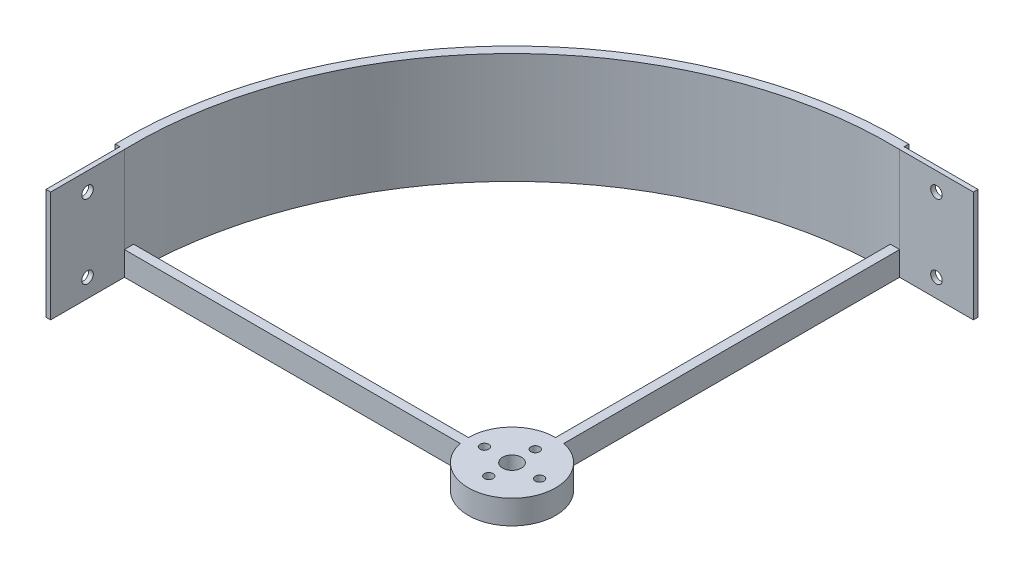
SolidWorks part; units mm, degrees
material "ABS"
ref_plane "Front Plane" through (0, 0, 0) normal (0, 0, 1) x (1, 0, 0)
ref_plane "Top Plane" through (0, 0, 0) normal (0, 1, 0) x (1, 0, 0)
ref_plane "Right Plane" through (0, 0, 0) normal (1, 0, 0) x (0, 0, -1)
sketch "Sketch1" plane through (0, 0, 0) normal (0, 1, 0) x (1, 0, 0)
  line L0 (0, 130.175) -> (0, 9.3426)
  line L1 (3.175, 9.3426) -> (3.175, 130.1363)
  line L2 (0, 0) -> (-22.0351, 22.0351) construction
  line L3 (-22.0351, 22.0351) -> (23.6345, -23.6345) construction
  line L4 (-9.3426, -3.175) -> (-130.1363, -3.175)
  line L5 (-130.175, 0) -> (-9.3426, 0)
  line L6 (3.175, 9.3426) -> (3.175, 130.1363)
  line L7 (3.175, 130.1363) -> (3.175, 133.3122)
  line L8 (-130.1363, -3.175) -> (-133.3122, -3.175)
  circle A0 centre (0, 0) radius 15
  arc A1 (3.175, 130.1363) -> (-130.1363, -3.175) centre (0, 0) ccw
  arc A2 (3.175, 133.3122) -> (-133.3122, -3.175) centre (0, 0) ccw
  dimension "D1" = 30
  dimension "D2" = 133.35
  dimension "D4" = 3.175
  dimension "D3" = 3.175
extrude "Boss-Extrude2" add sketch "Sketch1" along normal blind 8.255 contours A0
extrude "Boss-Extrude3" add sketch "Sketch1<6>" along normal blind 8.255 contours L5 A1 L4 A0 | L6 A1 L0 A0 region at (1.5882, 0, -72.5246) region at (-72.5246, 0, 1.5882)
sketch "Sketch1<6>" plane through (0, 0, 0) normal (0, 1, 0) x (1, 0, 0) same geometry as "Sketch1"
extrude "Boss-Extrude4" add sketch "Sketch1<7>" along normal blind 38.1 contours L7 A2 L8 A1 region at (-93.4129, 0, -93.4129)
sketch "Sketch1<7>" plane through (0, 0, 0) normal (0, 1, 0) x (1, 0, 0) same geometry as "Sketch1"
ref_plane "Plane1" through (-63.4806, 0, -63.4806) normal (0.7071, 0, 0.7071) x (0.7071, 0, -0.7071)
sketch "Sketch5" plane through (0, 8.255, 0) normal (0, 1, 0) x (1, 0, 0)
  line L0 (0, 0) -> (29.635, 0) construction
  line L1 (0, 0) -> (0, 21.5427) construction
  line L2 (0, 130.175) -> (0, 15) construction
  line L3 (0, 0) -> (29.22, 0) construction
  line L4 (21.3608, 0) -> (-27.7675, 0) construction
  line L5 (0, 0) -> (0, 21.6948) construction
  line L6 (0, 8) -> (0, 0) construction
  line L7 (0, 0) -> (37.8993, -60.1598) construction
  line L8 (0, 0) -> (-19.6346, 0) construction
  line L9 (-130.175, 0) -> (-15, 0) construction
  circle A0 centre (-9.5, 0) radius 1.5
  circle A1 centre (0, 8) radius 1.5
  circle A2 centre (0, -8) radius 1.5
  circle A3 centre (9.5, 0) radius 1.5
  circle A6 centre (0, 0) radius 3.25
  point P18 (0, 0)
  dimension "D3" = 3
  dimension "D7" = 3
  dimension "D8" = 6.5
  dimension "D2" = 8
  dimension "D5" = 90
  dimension "D6" = 8
  dimension "D9" = 90
  dimension "D10" = 9.5
  dimension "D4" = 57.79
extrude "Cut-Extrude3" cut sketch "Sketch5" against normal blind 63.5
sketch "Sketch6" plane through (0, 0, 3.175) normal (0, 0, 1) x (1, 0, 0)
  line L0 (-14.6601, 0) -> (-133.3122, 0) construction
  line L1 (-130.1363, 38.1) -> (-131.7242, 38.1)
  line L2 (-130.1363, 38.1) -> (-130.1363, 0)
  line L3 (-130.1363, 0) -> (-131.7242, 0)
  line L4 (-131.7242, 38.1) -> (-131.7242, 0)
  line L5 (-130.1363, 38.1) -> (-133.3122, 38.1) construction
  point P7 (-131.7242, 38.1)
extrude "Boss-Extrude5" add sketch "Sketch6" along normal blind 25.4
sketch "Sketch7" plane through (3.175, 0, 0) normal (1, 0, 0) x (0, 0, -1)
  line L0 (14.6601, 0) -> (133.3122, 0) construction
  line L1 (130.1363, 38.1) -> (131.7242, 38.1)
  line L2 (130.1363, 38.1) -> (130.1363, 0)
  line L3 (130.1363, 0) -> (131.7242, 0)
  line L4 (131.7242, 38.1) -> (131.7242, 0)
  line L5 (130.1363, 38.1) -> (133.3122, 38.1) construction
  line L6 (130.1363, 38.1) -> (130.1363, 8.255) construction
  point P7 (131.7242, 38.1)
extrude "Boss-Extrude6" add sketch "Sketch7" along normal blind 25.4
sketch "Sketch8" plane through (-131.7242, 0, 0) normal (-1, 0, 0) x (0, 0, 1)
  line L0 (3.175, 19.05) -> (28.575, 19.05) construction
  line L1 (3.175, 38.1) -> (3.175, 0) construction
  line L2 (28.575, 38.1) -> (28.575, 0) construction
  line L3 (15.875, 19.05) -> (15.875, 31.75) construction
  circle A0 centre (15.875, 31.75) radius 1.9844
  circle A1 centre (15.875, 6.35) radius 1.9844
  dimension "D1" = 3.9688
  dimension "D2" = 12.7
extrude "Cut-Extrude4" cut sketch "Sketch8" against normal up to surface (1.588 mm away) up to face at (-130.1363, 16.891, 13.335)
sketch "Sketch9" plane through (0, 0, -131.7242) normal (0, 0, -1) x (-1, 0, 0)
  line L0 (-28.575, 19.05) -> (-3.175, 19.05) construction
  line L1 (-28.575, 0) -> (-28.575, 38.1) construction
  line L2 (-3.175, 0) -> (-3.175, 38.1) construction
  line L3 (-15.875, 19.05) -> (-15.875, 31.75) construction
  circle A0 centre (-15.875, 31.75) radius 1.9844
  circle A1 centre (-15.875, 6.35) radius 1.9844
  dimension "D1" = 3.9688
  dimension "D2" = 12.7
extrude "Cut-Extrude5" cut sketch "Sketch9" against normal up to surface (1.588 mm away) up to face at (13.335, 16.891, -130.1363)
